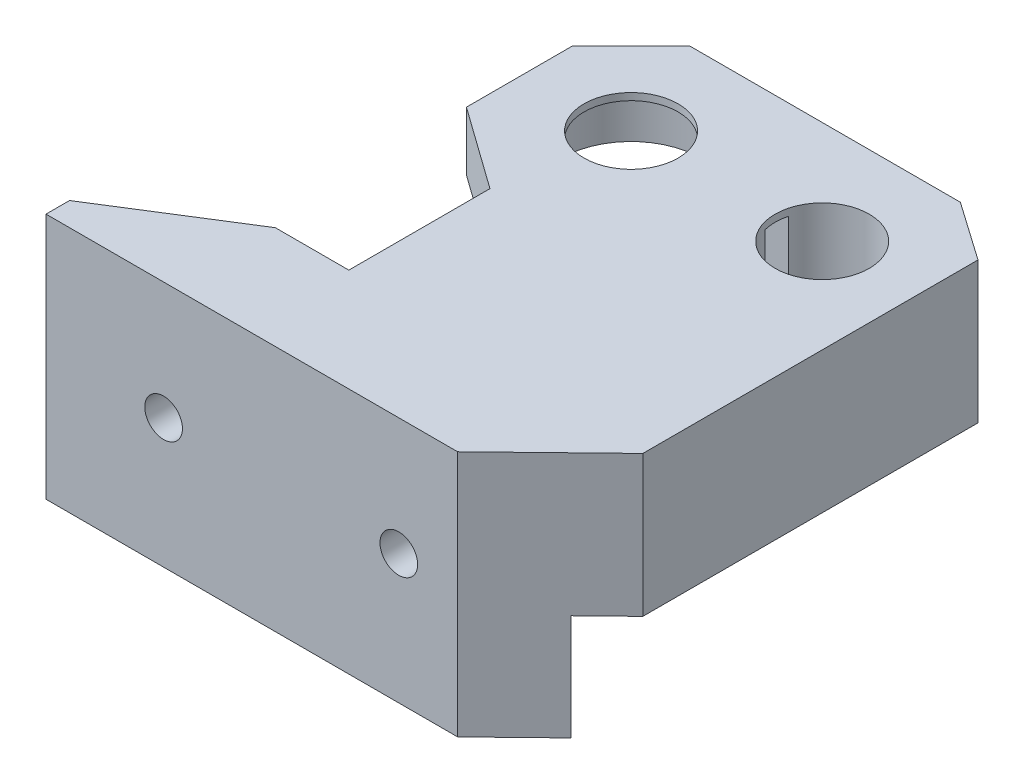
SolidWorks part; units mm, degrees
ref_plane "Front Plane" through (0, 0, 0) normal (0, 0, 1) x (1, 0, 0)
ref_plane "Top Plane" through (0, 0, 0) normal (0, 1, 0) x (1, 0, 0)
ref_plane "Right Plane" through (0, 0, 0) normal (1, 0, 0) x (0, 0, -1)
sketch "Sketch1" plane through (0, 0, 0) normal (0, 1, 0) x (1, 0, 0)
  line L0 (0, 0) -> (16.25, 0) construction
  line L5 (-3.75, 8.75) -> (19.25, 8.75)
  line L6 (19.25, 8.75) -> (24.25, 5.25)
  line L7 (24.25, 5.25) -> (24.25, -23.25)
  line L8 (24.25, -23.25) -> (16.25, -31)
  line L9 (16.25, -31) -> (-18.75, -31)
  line L10 (-18.75, -31) -> (-18.75, -29)
  line L11 (-18.75, -29) -> (-8, -22.25)
  line L12 (-8, -22.25) -> (-1.75, -22.25)
  line L13 (-1.75, -22.25) -> (-1.75, -10.25)
  line L14 (-1.75, -10.25) -> (-8.75, -5.25)
  line L15 (-8.75, -5.25) -> (-8.75, 3.75)
  line L16 (-8.75, 3.75) -> (-3.75, 8.75)
  line L17 (16.25, 0) -> (24.25, 0) construction
  circle A0 centre (0, 0) radius 4
  circle A1 centre (16.25, 0) radius 4
  point P0 (0, 0)
  dimension "D2" = 8
  dimension "D3" = 8
  dimension "D1" = 16.25
  dimension "D4" = 23
  dimension "D5" = 5
  dimension "D6" = 3.5
  dimension "D7" = 28.5
  dimension "D8" = 8
  dimension "D9" = 8.75
  dimension "D10" = 5
  dimension "D11" = 5
  dimension "D12" = 7
  dimension "D13" = 5
  dimension "D14" = 9
  dimension "D15" = 8
  dimension "D16" = 7.75
  dimension "D17" = 35
  dimension "D18" = 6.25
  dimension "D19" = 6.75
  dimension "D20" = 2
extrude "Boss-Extrude1" add sketch "Sketch1" along normal blind 5
sketch "Sketch2" plane through (0, 0, 0) normal (0, -1, 0) x (1, 0, 0)
  line L0 (24.25, 23.25) -> (24.25, -5.25)
  line L1 (24.25, -5.25) -> (20.75, -5.25)
  line L2 (20.75, -5.25) -> (20.75, 22.25)
  line L3 (20.75, 22.25) -> (-8, 22.25)
  line L4 (-8, 22.25) -> (-14.3704, 26.25)
  line L5 (-8, 22.25) -> (-18.75, 29) construction
  line L6 (-14.3704, 26.25) -> (21.1532, 26.25)
  line L7 (16.25, 31) -> (24.25, 23.25) construction
  line L8 (21.1532, 26.25) -> (24.25, 23.25)
  dimension "D1" = 3.5
  dimension "D2" = 4
extrude "Boss-Extrude2" add sketch "Sketch2" along normal blind 7
sketch "Sketch3" plane through (0, 0, 0) normal (0, -1, 0) x (1, 0, 0)
  line L5 (-14.3704, 26.25) -> (21.1532, 26.25)
  line L6 (21.1532, 26.25) -> (16.25, 31)
  line L7 (16.25, 31) -> (-18.75, 31)
  line L8 (-18.75, 31) -> (-18.75, 29)
  line L9 (-18.75, 29) -> (-14.3704, 26.25)
  line L10 (-14.3704, 26.25) -> (21.1532, 26.25)
  line L11 (21.1532, 26.25) -> (16.25, 31)
  line L12 (16.25, 31) -> (-18.75, 31)
  line L13 (-18.75, 31) -> (-18.75, 29)
  line L14 (-18.75, 29) -> (-14.3704, 26.25)
  dimension "D1" = 0
extrude "Boss-Extrude3" add sketch "Sketch3" along normal blind 16
sketch "Sketch6" plane through (0, 0, 0) normal (0, -1, 0) x (1, 0, 0)
  circle A0 centre (16.25, 0) radius 7
  circle A1 centre (16.25, 0) radius 4
  dimension "D1" = 14
extrude "Boss-Extrude4" add sketch "Sketch6" along normal blind 2.5
sketch "Sketch4" plane through (0, 0, 0) normal (0, -1, 0) x (1, 0, 0)
  line L0 (0, 0) -> (12.25, 0) construction
  line L1 (5.8838, -1) -> (12.377, -1)
  line L2 (5.8838, 1) -> (12.377, 1)
  line L3 (0, -1) -> (16.25, -1) construction
  line L4 (0, 1) -> (16.25, 1) construction
  line L5 (0, 0) -> (16.25, 0) construction
  arc A0 (5.8838, 1) -> (5.8838, -1) centre (0, 0) ccw
  arc A2 (12.377, 1) -> (12.377, -1) centre (16.25, 0) ccw
  dimension "D1" = 1
  dimension "D2" = 1
extrude "Cut-Extrude1" cut sketch "Sketch4" against normal blind 4.4
sketch "Sketch7" plane through (0, 4.4, 0) normal (0, -1, 0) x (1, 0, 0)
  line L2 (5.8838, -1) -> (12.377, -1)
  line L3 (12.377, 1) -> (5.8838, 1)
  line L4 (5.8838, -1) -> (12.377, -1)
  line L5 (12.377, 1) -> (5.8838, 1)
  arc A2 (5.8838, 1) -> (5.8838, -1) centre (0, 0) ccw
  arc A3 (12.377, 1) -> (12.377, -1) centre (16.25, 0) ccw
  arc A4 (5.8838, 1) -> (5.8838, -1) centre (0, 0) ccw
  arc A5 (12.377, 1) -> (12.377, -1) centre (16.25, 0) ccw
  dimension "D1" = 0
extrude "Cut-Extrude2" cut sketch "Sketch7" along normal through all
sketch "Sketch8" plane through (0, 0, 31) normal (0, 0, 1) x (1, 0, 0)
  line L0 (11.25, -5) -> (-8.75, -5) construction
  line L1 (-18.75, 5) -> (16.25, 5) construction
  line L2 (-18.75, 5) -> (-18.75, -16) construction
  circle A0 centre (11.25, -5) radius 1.6
  circle A1 centre (-8.75, -5) radius 1.6
  dimension "D1" = 3.2
  dimension "D2" = 3.2
  dimension "D3" = 20
  dimension "D4" = 10
  dimension "D5" = 10
extrude "Cut-Extrude3" cut sketch "Sketch8" against normal through all
sketch "Sketch9" plane through (0, 0, 22.25) normal (0, 0, -1) x (-1, 0, 0)
  circle A0 centre (-11.25, -5) radius 3
  circle A1 centre (8.75, -5) radius 3
  dimension "D1" = 6
  dimension "D2" = 6
extrude "Cut-Extrude4" cut sketch "Sketch9" against normal blind 4
